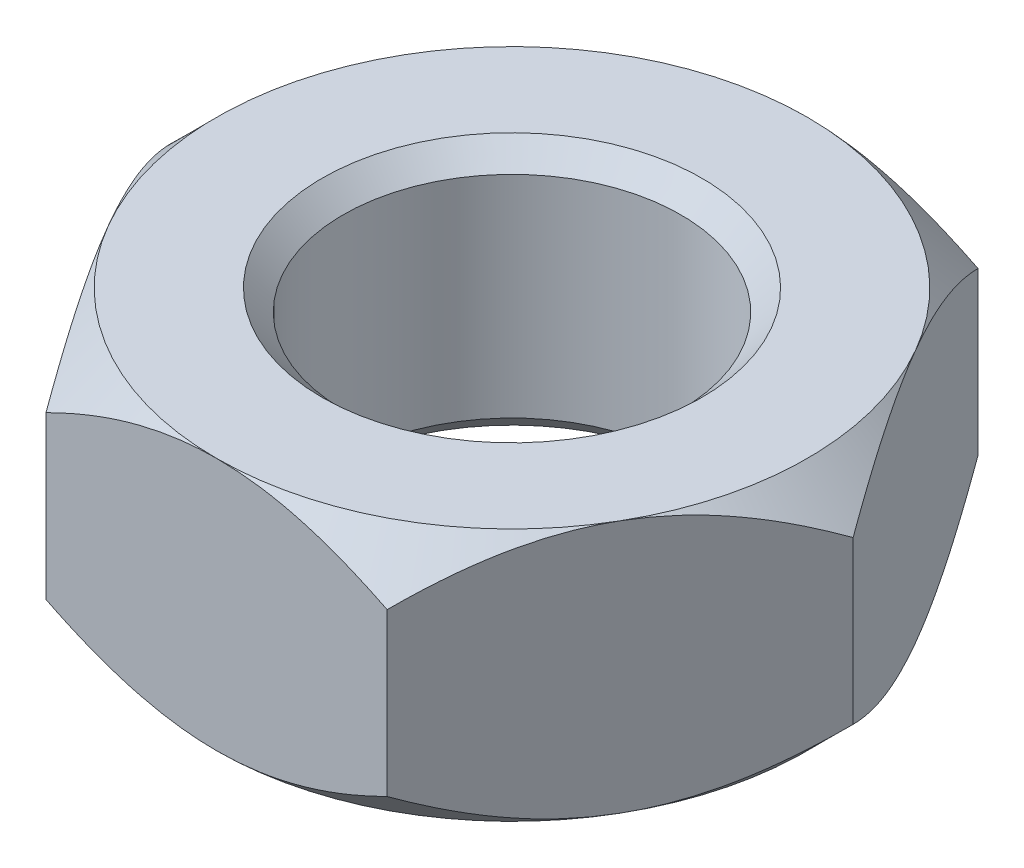
SolidWorks part; units mm, degrees
ref_plane "Front Plane" through (0, 0, 0) normal (0, 0, 1) x (1, 0, 0)
ref_plane "Top Plane" through (0, 0, 0) normal (0, 1, 0) x (1, 0, 0)
ref_plane "Right Plane" through (0, 0, 0) normal (1, 0, 0) x (0, 0, -1)
sketch "Sketch1" plane through (0, 0, 0) normal (0, 1, 0) x (1, 0, 0)
  line L1 (4.0415, 0) -> (2.0207, 3.5)
  line L2 (2.0207, 3.5) -> (-2.0207, 3.5)
  line L3 (-2.0207, 3.5) -> (-4.0415, 0)
  line L4 (-4.0415, 0) -> (-2.0207, -3.5)
  line L5 (-2.0207, -3.5) -> (2.0207, -3.5)
  line L6 (2.0207, -3.5) -> (4.0415, 0)
  circle A0 centre (0, 0) radius 3.5 construction
  circle A1 centre (0, 0) radius 2
  dimension "D2" = 4
  dimension "D1" = 7
extrude "Boss-Extrude1" add sketch "Sketch1" along normal blind 3 contours L5 L6 L1 L2 L3 L4 A1 region at (2.9385, 0, 1.6965)
sketch "Sketch2" plane through (0, 0, 0) normal (1, 0, 0) x (0, 0, -1)
  line L0 (3.5, 3) -> (4.55, 4.05)
  line L1 (4.55, 4.05) -> (4.55, 1.95)
  line L2 (4.55, 1.95) -> (3.5, 3)
  line L3 (3.5, 1.5) -> (7.8632, 1.5) construction
  line L4 (3.5, 3) -> (3.5, 0) construction
  line L5 (4.55, 1.05) -> (3.5, 0)
  line L6 (4.55, -1.05) -> (4.55, 1.05)
  line L7 (3.5, 0) -> (4.55, -1.05)
  dimension "D1" = 2.1
ref_axis "Axis1" through (0, 3, 0) along (0, -1, 0)
revolve "Cut-Revolve1" cut sketch "Sketch2" angle 360 about axis through (0, 3, 0) along (0, -1, 0)
sketch "Sketch4" plane through (0, 3, 0) normal (0, 1, 0) x (1, 0, 0)
  circle A0 centre (0, 0) radius 4
curve "Helix/Spiral1" [suppressed] pitch 1.25 height 5 turns 4
ref_plane "Plane1" [suppressed] through (0, 5, 4) normal (-0.9988, -0.0497, 0) x (0, 0, 1)
chamfer "Chamfer1" [suppressed] distance 0.5 angle 45
sketch "Sketch5" [suppressed] plane through (0, 5, 4) normal (-0.9988, -0.0497, 0) x (0, 0, 1)
  line L0 (0.4983, 0.146) -> (-0.8007, 0.896)
  line L1 (-0.8007, 0.896) -> (-0.8007, -0.604)
  line L2 (-0.8007, -0.604) -> (0.4983, 0.146)
  line L3 (-0.0006, -0.854) -> (0.1004, -0.854) construction
  dimension "D1" = 1.5
ref_axis "Axis2" through (0, 3, 0) along (0, -1, 0)
chamfer "Chamfer2" distance 0.25 angle 45 2 edges at (0, 3, 2) (0, 0, 2)
